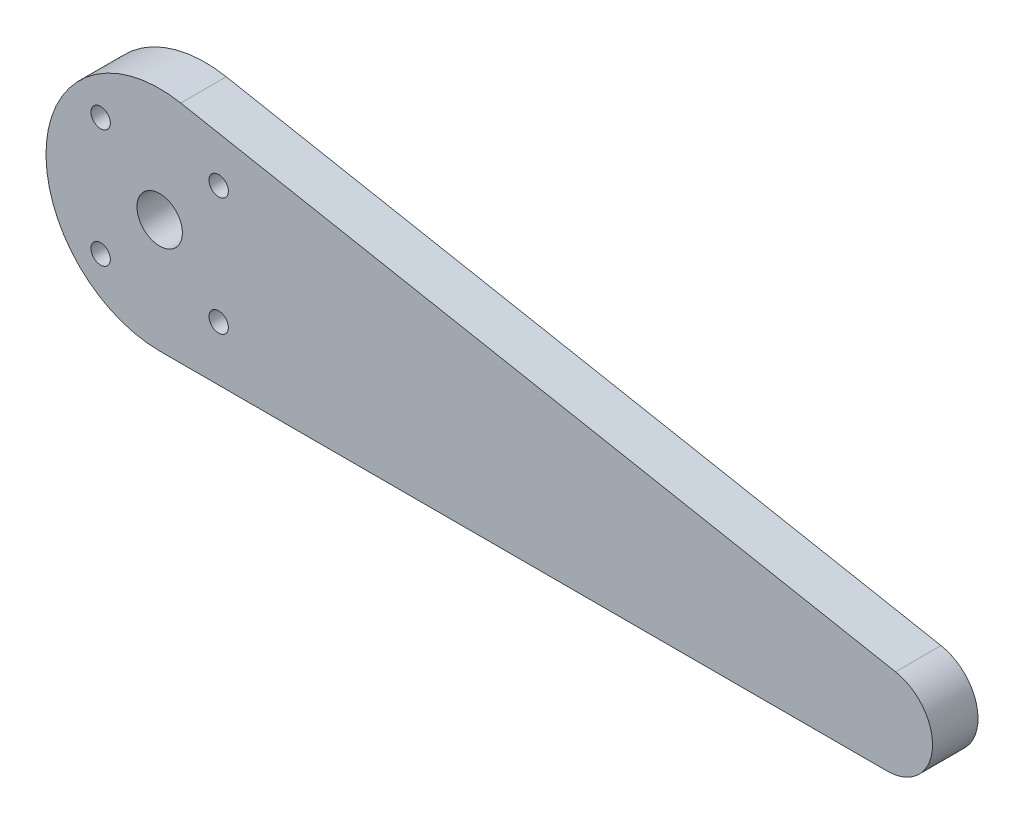
SolidWorks part; units mm, degrees
material "6061 Alloy"
ref_plane "Front" through (0, 0, 0) normal (0, 0, 1) x (1, 0, 0)
ref_plane "Top" through (0, 0, 0) normal (0, 1, 0) x (1, 0, 0)
ref_plane "Right" through (0, 0, 0) normal (1, 0, 0) x (0, 0, -1)
sketch "Sketch1" plane through (0, 0, 0) normal (0, 0, 1) x (1, 0, 0)
  line L0 (0, -15.875) -> (101.6, -15.875)
  line L1 (2.9506, 15.5984) -> (102.7803, -3.2856)
  line L2 (8.2424, 8.2424) -> (-8.2424, -8.2424) construction
  line L3 (-8.2424, 8.2424) -> (8.2424, -8.2424) construction
  arc A0 (2.9506, 15.5984) -> (0, -15.875) centre (0, 0) ccw
  circle A1 centre (0, 0) radius 3.175
  circle A6 centre (0, 0) radius 11.6565 construction
  circle A7 centre (8.2424, 8.2424) radius 1.3525 construction
  circle A8 centre (-8.2424, 8.2424) radius 1.3525 construction
  circle A9 centre (-8.2424, -8.2424) radius 1.3525 construction
  circle A10 centre (8.2424, -8.2424) radius 1.3525 construction
  arc A11 (101.6, -15.875) -> (102.7803, -3.2856) centre (101.6, -9.525) ccw
  point P10 (129.0327, -15.875)
  point P11 (115.3811, 2.0087)
  dimension "D1" = 6.35
  dimension "D2" = 31.75
  dimension "D3" = 6.35
  dimension "D4" = 101.6
  dimension "D7" = 23.313
  dimension "D8" = 2.7051
extrude "Boss-Extrude1" add sketch "Sketch1" along normal blind 6.35
hole_wizard "#6-32 Tapped Hole1" positions "Sketch2" profile "Sketch3" tap size "#6-32" standard "ANSI Inch" end condition through all
sketch "Sketch2" plane through (0, 0, 6.35) normal (0, 0, 1) x (1, 0, 0)
  point P0 (8.2424, 8.2424)
  point P3 (-8.2424, 8.2424)
  point P6 (8.2424, -8.2424)
  point P9 (-8.2424, -8.2424)
sketch "Sketch3" plane through (8.2424, 8.2424, 6.35) normal (1, 0, 0) x (0, -1, 0)
  line L0 (0, 0) -> (0, 6.35)
  line L1 (0, 6.35) -> (1.3525, 6.35)
  line L2 (1.3525, 6.35) -> (1.3525, 0)
  line L5 (1.3525, 0) -> (0, 0)
  line L11 (0, -6.35) -> (0, 107.95) construction
  dimension "Thru Tap Drill Dia." = 2.7051
  dimension "Thru Tap Drill Depth" = 6.35
